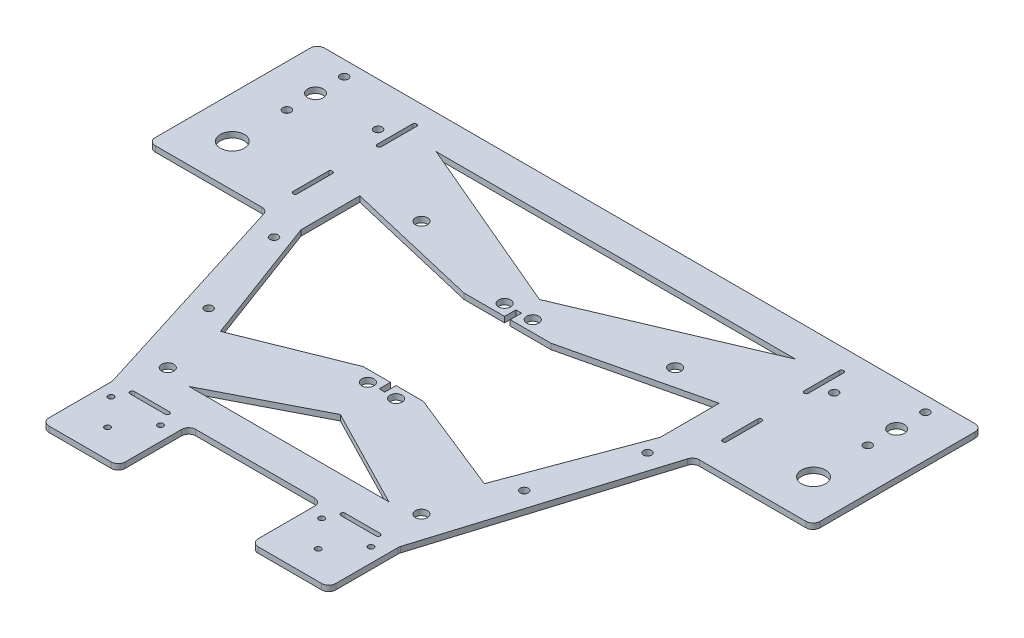
SolidWorks part; units mm, degrees
ref_plane "Front Plane" through (0, 0, 0) normal (0, 0, 1) x (1, 0, 0)
ref_plane "Top Plane" through (0, 0, 0) normal (0, 1, 0) x (1, 0, 0)
ref_plane "Right Plane" through (0, 0, 0) normal (1, 0, 0) x (0, 0, -1)
sketch "Sketch26" plane through (0, 0, 0) normal (0, 1, 0) x (1, 0, 0)
  line L0 (76.0133, 28.8235) -> (76.0133, 88.8235) construction
  line L1 (-63.5382, 76.8235) -> (64.0673, 76.8235)
  line L2 (0.2645, 93.3283) -> (0.2645, -99.0046) construction
  line L3 (21.3527, -51.1765) -> (-20.8236, -51.1765)
  line L4 (76.0133, 88.8235) -> (-76.0328, 88.8235)
  line L5 (-75.4842, 28.8235) -> (-75.4842, 88.8235) construction
  line L6 (115.6892, 88.8235) -> (76.0133, 88.8235)
  line L7 (-77.3206, 28.8235) -> (-115.1602, 28.8235)
  line L8 (-74.935, 27.0713) -> (-50.5239, -50.8121)
  line L9 (75.4699, 27.0594) -> (51.4834, -50.8168)
  line L10 (-117.6602, 31.3235) -> (-117.6602, 86.3235)
  line L11 (-115.1602, 88.8235) -> (-75.4842, 88.8235)
  line L12 (-75.91, 39.1911) -> (-75.91, 51.6911) construction
  line L13 (-76.66, 39.1911) -> (-76.66, 51.6911)
  line L14 (-75.16, 39.1911) -> (-75.16, 51.6911)
  line L15 (-75.4842, 81.0951) -> (-75.4842, 68.5951) construction
  line L16 (-74.7342, 81.0951) -> (-74.7342, 68.5951)
  line L17 (118.1892, 31.3235) -> (118.1892, 86.3235)
  line L18 (-76.2342, 81.0951) -> (-76.2342, 68.5951)
  line L19 (-46.5438, -16.6765) -> (-10.4029, -2.1765)
  line L20 (77.8592, 28.8235) -> (115.6892, 28.8235)
  line L21 (64.0133, 49.7097) -> (64.0133, 28.8235)
  line L22 (64.0133, 28.8235) -> (47.0729, -16.6765)
  line L23 (-63.4842, 28.8235) -> (-46.5438, -16.6765)
  line L24 (47.0729, -16.6765) -> (10.932, -2.1765)
  line L25 (15.7075, 38.3235) -> (64.0133, 49.7097)
  line L26 (-63.4842, 49.7097) -> (-63.4842, 28.8235)
  line L27 (1.2645, 42.3235) -> (1.2645, 38.3235)
  line L28 (1.2645, 42.3235) -> (-0.7355, 42.3235)
  line L29 (1.2645, 38.3235) -> (15.7075, 38.3235)
  line L30 (-0.7355, 42.3235) -> (-0.7355, 38.3235)
  line L31 (64.0673, 76.8235) -> (0.2645, 49.7097)
  line L32 (-0.7355, 38.3235) -> (-15.1784, 38.3235)
  line L33 (76.0133, 81.0951) -> (76.0133, 68.5951) construction
  line L34 (-15.1784, 38.3235) -> (-63.4842, 49.7097)
  line L35 (-63.5382, 76.8235) -> (0.2645, 49.7097)
  line L36 (1.2645, -2.1765) -> (10.932, -2.1765)
  line L37 (75.2633, 81.0951) -> (75.2633, 68.5951)
  line L38 (1.2645, -6.1765) -> (1.2645, -2.1765)
  line L39 (1.2645, -6.1765) -> (-0.7355, -6.1765)
  line L40 (-0.7355, -6.1765) -> (-0.7355, -2.1765)
  line L41 (-0.7355, -2.1765) -> (-10.4029, -2.1765)
  line L42 (-35.1832, -39.1765) -> (35.7123, -39.1765)
  line L43 (0.2645, -20.9512) -> (35.7123, -39.1765)
  line L44 (0.2645, -20.9512) -> (-35.1832, -39.1765)
  line L45 (51.3727, -51.5527) -> (51.3727, -73.6765)
  line L46 (48.8727, -76.1765) -> (26.3527, -76.1765)
  line L47 (76.7633, 81.0951) -> (76.7633, 68.5951)
  line L48 (76.4391, 39.1911) -> (76.4391, 51.6911) construction
  line L49 (77.1891, 39.1911) -> (77.1891, 51.6911)
  line L50 (75.6891, 39.1911) -> (75.6891, 51.6911)
  line L51 (23.8527, -73.6765) -> (23.8527, -53.6765)
  line L52 (37.6127, -76.1765) -> (37.6127, -51.1765) construction
  line L53 (51.3727, -76.1765) -> (51.3727, -51.1765)
  line L54 (23.8527, -51.1765) -> (23.8527, -76.1765)
  line L55 (-50.4095, -51.5599) -> (-50.4095, -73.6765)
  line L56 (-47.9095, -76.1765) -> (-25.8236, -76.1765)
  line L57 (-23.3236, -73.6765) -> (-23.3236, -53.6765)
  line L58 (31.4072, -51.1727) -> (43.9072, -51.1727) construction
  line L59 (31.4072, -50.4227) -> (43.9072, -50.4227)
  line L60 (31.4072, -51.9227) -> (43.9072, -51.9227)
  line L61 (-30.8781, -51.1727) -> (-43.3781, -51.1727) construction
  line L62 (-30.8781, -50.4227) -> (-43.3781, -50.4227)
  line L63 (-30.8781, -51.9227) -> (-43.3781, -51.9227)
  circle A0 centre (45.2645, 52.8235) radius 2.15
  circle A1 centre (45.2645, -37.1765) radius 2.15
  circle A2 centre (5.2645, 42.3235) radius 2.15
  circle A3 centre (5.2645, -6.1765) radius 2.15
  circle A4 centre (103.3673, 43.8235) radius 4.25
  arc A5 (118.1892, 31.3235) -> (115.6892, 28.8235) centre (115.6892, 31.3235) cw
  circle A6 centre (103.3673, 73.3235) radius 2.75
  circle A7 centre (103.3673, 83.5235) radius 1.45
  circle A8 centre (103.3133, 63.1237) radius 1.45
  circle A9 centre (81.1673, 73.3235) radius 1.45
  arc A10 (118.1892, 86.3235) -> (115.6892, 88.8235) centre (115.6892, 86.3235) ccw
  arc A11 (-117.6602, 86.3235) -> (-115.1602, 88.8235) centre (-115.1602, 86.3235) cw
  circle A12 centre (-80.6382, 73.3235) radius 1.45
  circle A13 centre (-102.7842, 63.1237) radius 1.45
  circle A14 centre (-102.8382, 83.5235) radius 1.45
  circle A15 centre (-102.8382, 73.3235) radius 2.75
  arc A16 (-117.6602, 31.3235) -> (-115.1602, 28.8235) centre (-115.1602, 31.3235) ccw
  arc A17 (75.2633, 81.0951) -> (76.7633, 81.0951) centre (76.0133, 81.0951) cw
  circle A18 centre (-102.8382, 43.8235) radius 4.25
  circle A19 centre (-4.7355, -6.1765) radius 2.15
  arc A20 (76.7633, 68.5951) -> (75.2633, 68.5951) centre (76.0133, 68.5951) cw
  arc A21 (77.1891, 39.1911) -> (75.6891, 39.1911) centre (76.4391, 39.1911) cw
  arc A22 (75.6891, 51.6911) -> (77.1891, 51.6911) centre (76.4391, 51.6911) cw
  circle A23 centre (-4.7355, 42.3235) radius 2.15
  circle A24 centre (-44.7355, -37.1765) radius 2.15
  circle A25 centre (-44.7355, 52.8235) radius 2.15
  arc A26 (-76.66, 39.1911) -> (-75.16, 39.1911) centre (-75.91, 39.1911) ccw
  arc A27 (-75.16, 51.6911) -> (-76.66, 51.6911) centre (-75.91, 51.6911) ccw
  arc A28 (-74.7342, 81.0951) -> (-76.2342, 81.0951) centre (-75.4842, 81.0951) ccw
  arc A29 (-76.2342, 68.5951) -> (-74.7342, 68.5951) centre (-75.4842, 68.5951) ccw
  circle A30 centre (28.8527, -56.1765) radius 1
  circle A31 centre (37.6127, -66.1765) radius 1
  circle A32 centre (46.3727, -56.1765) radius 1
  circle A33 centre (28.8527, -56.1765) radius 1
  circle A34 centre (46.3727, -56.1765) radius 1
  circle A35 centre (-28.3236, -56.1765) radius 1
  circle A36 centre (-45.8436, -56.1765) radius 1
  circle A37 centre (-37.0836, -66.1765) radius 1
  arc A38 (31.4072, -50.4227) -> (31.4072, -51.9227) centre (31.4072, -51.1727) ccw
  arc A39 (43.9072, -51.9227) -> (43.9072, -50.4227) centre (43.9072, -51.1727) ccw
  arc A40 (-30.8781, -50.4227) -> (-30.8781, -51.9227) centre (-30.8781, -51.1727) cw
  arc A41 (-43.3781, -51.9227) -> (-43.3781, -50.4227) centre (-43.3781, -51.1727) cw
  arc A42 (77.8592, 28.8235) -> (75.4699, 27.0594) centre (77.8592, 26.3235) ccw
  arc A43 (-74.935, 27.0713) -> (-77.3206, 28.8235) centre (-77.3206, 26.3235) ccw
  arc A44 (51.3727, -51.5527) -> (51.4834, -50.8168) centre (53.8727, -51.5527) cw
  arc A45 (21.3527, -51.1765) -> (23.8527, -53.6765) centre (21.3527, -53.6765) cw
  arc A46 (-20.8236, -51.1765) -> (-23.3236, -53.6765) centre (-20.8236, -53.6765) ccw
  arc A47 (-50.4095, -51.5599) -> (-50.5239, -50.8121) centre (-52.9095, -51.5599) ccw
  arc A48 (-23.3236, -73.6765) -> (-25.8236, -76.1765) centre (-25.8236, -73.6765) cw
  arc A49 (-47.9095, -76.1765) -> (-50.4095, -73.6765) centre (-47.9095, -73.6765) cw
  circle A50 centre (66.5151, 21.7665) radius 1.45
  circle A51 centre (56.2618, -11.698) radius 1.45
  circle A52 centre (-55.7328, -11.698) radius 1.45
  circle A53 centre (-65.9861, 21.7665) radius 1.45
  arc A54 (48.8727, -76.1765) -> (51.3727, -73.6765) centre (48.8727, -73.6765) ccw
  arc A55 (26.3527, -76.1765) -> (23.8527, -73.6765) centre (26.3527, -73.6765) cw
  circle A56 centre (0.2645, 7.8235) radius 1.4516
  point P60 (-75.91, 45.4411)
  point P63 (76.0133, 74.8451)
  point P71 (76.4391, 45.4411)
  point P77 (-75.4842, 74.8451)
  point P99 (0.2645, 42.3235)
  point P107 (0.2645, -6.1765)
  point P112 (0.2645, -39.1765)
  point P136 (37.6572, -51.1727)
  point P143 (-37.1281, -51.1727)
  point P162 (-23.3236, -51.1765)
  point P167 (-23.3236, -76.1765)
  dimension "D6" = 4.3
  dimension "D13" = 8.5
  dimension "D14" = 2.9
  dimension "D15" = 2.9
  dimension "D16" = 2.9
  dimension "D10" = 2.5
  dimension "D21" = 2.5
  dimension "D3" = 45
  dimension "D7" = 4.3
  dimension "D8" = 5.5
  dimension "D22" = 45
  dimension "D4" = 48.5
  dimension "D11" = 4.3
  dimension "D24" = 4.3
  dimension "D28" = 5
  dimension "D36" = 15
  dimension "D37" = 2.5
  dimension "D38" = 2.9
  dimension "D41" = 2.9
  dimension "D40" = 2.5
  dimension "D5" = 90
  dimension "D12" = 15
  dimension "D17" = 10.2
  dimension "D18" = 10.2
  dimension "D19" = 22.2
  dimension "D20" = 29.5
  dimension "D9" = 40
  dimension "D23" = 40
  dimension "D25" = 36
  dimension "D26" = 45
  dimension "D27" = 12
  dimension "D29" = 12
  dimension "D30" = 12
  dimension "D31" = 1
  dimension "D32" = 4
  dimension "D33" = 27.52
  dimension "D34" = 25
  dimension "D35" = 5
  dimension "D39" = 7
  dimension "D42" = 35
  dimension "D43" = 14
  dimension "D44" = 4
  dimension "D45" = 4
  dimension "D46" = 4
extrude "Boss-Extrude4" add sketch "Sketch26" along normal blind 2 contours L20 A5 L17 A10 A20 region at (0.2645, 0, 48.2981)
